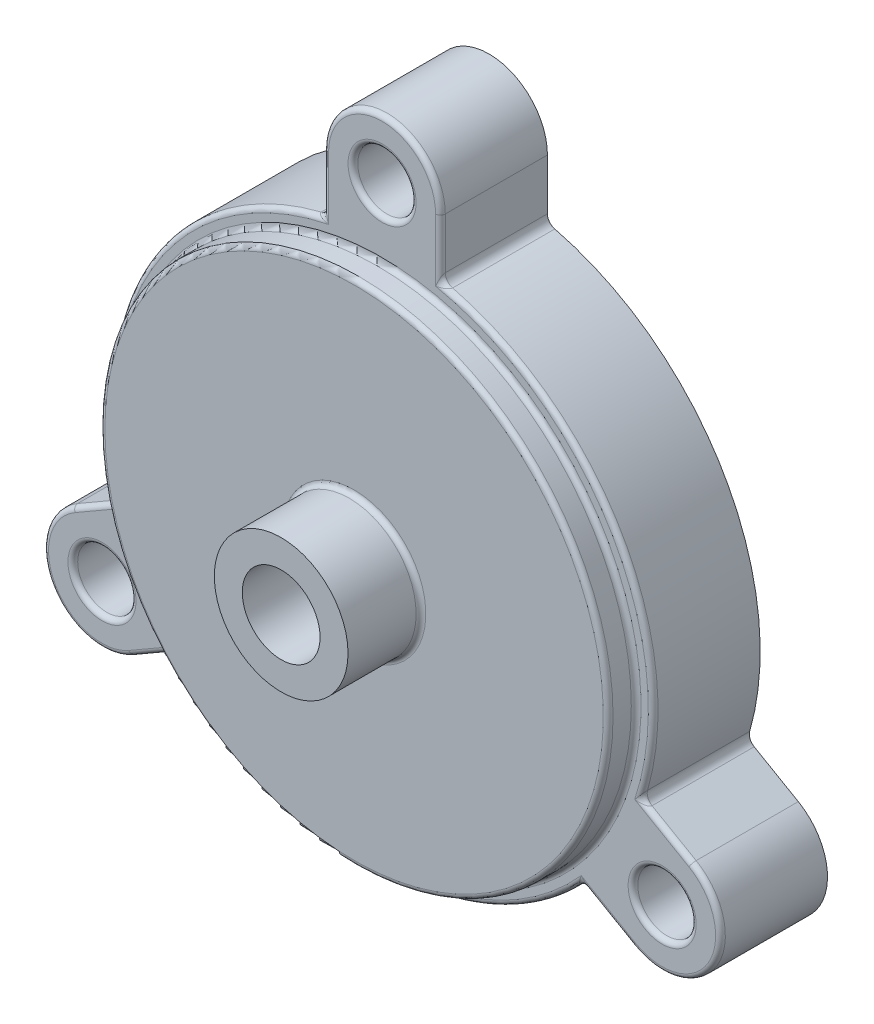
SolidWorks part; units mm, degrees
material "PE Low/Medium Density"
ref_plane "Front Plane" through (0, 0, 0) normal (0, 0, 1) x (1, 0, 0)
ref_plane "Top Plane" through (0, 0, 0) normal (0, 1, 0) x (1, 0, 0)
ref_plane "Right Plane" through (0, 0, 0) normal (1, 0, 0) x (0, 0, -1)
sketch "Sketch1" plane through (0, 0, 0) normal (1, 0, 0) x (0, 0, -1)
  line L0 (1.4605, 14.1605) -> (1.4605, 13.2715)
  line L1 (0, 0) -> (7.62, 0) construction
  line L2 (0, 12.2555) -> (0, 13.2715)
  line L3 (1.4605, 14.1605) -> (7.0485, 14.1605)
  line L4 (7.62, 12.2555) -> (7.62, 12.9159)
  line L5 (1.4605, 13.2715) -> (0, 13.2715)
  line L6 (7.0485, 14.1605) -> (7.0485, 12.9159)
  line L7 (7.0485, 12.9159) -> (7.62, 12.9159)
  line L8 (0, 12.2555) -> (0, 0)
  line L9 (0, 0) -> (1.4605, 0)
  line L10 (7.62, 12.2555) -> (1.4605, 12.2555)
  line L11 (1.4605, 12.2555) -> (1.4605, 0)
  dimension "D1" = 5.588
  dimension "D2" = 7.62
  dimension "D3" = 0.5715
  dimension "D4" = 14.1605
  dimension "D5" = 1.016
  dimension "D6" = 1.905
  dimension "D7" = 0.6604
revolve "Base revolve" add sketch "Sketch1" angle 360 about L1
sketch "Sketch3" plane through (0, 0, -7.0485) normal (0, 0, -1) x (-1, 0, 0)
  line L0 (-3.048, 16.891) -> (-3.048, 13.8286)
  line L1 (3.048, 16.891) -> (3.048, 13.8286)
  line L2 (0, 0) -> (0, 22.6145) construction
  arc A0 (3.048, 16.891) -> (-3.048, 16.891) centre (0, 16.891) ccw
  circle A1 centre (0, 0) radius 14.1605 construction
  circle A2 centre (0, 16.891) radius 1.524
  arc A3 (-3.048, 13.8286) -> (3.048, 13.8286) centre (0, 0) cw
  point P12 (0, 19.939)
  dimension "D1" = 3.048
  dimension "D2" = 3.048
  dimension "D3" = 16.891
extrude "Flange" add sketch "Sketch3" against normal up to surface (5.588 mm away) up to face at (13.2715, 0, -1.4605)
pattern_circular "Circular pattern for flanges" count 3 over 360 about axis through (0, 0, -1.4605) along (0, 0, 1) of "Flange"
sketch "Sketch4" plane through (0, 0, -7.62) normal (0, 0, -1) x (-1, 0, 0)
  line L0 (-1.524, 14.2514) -> (-1.524, 12.1604)
  line L1 (1.524, 14.2514) -> (1.524, 12.1604)
  line L2 (-1.524, 16.891) -> (-1.524, 14.2514) construction
  line L3 (1.524, 16.891) -> (1.524, 14.2514) construction
  arc A0 (-1.524, 14.2514) -> (1.524, 14.2514) centre (0, 16.891) ccw
  circle A1 centre (0, 16.891) radius 1.524 construction
  circle A2 centre (0, 0) radius 12.2555 construction
  circle A3 centre (0, 0) radius 12.2555 construction
  arc A4 (-1.524, 12.1604) -> (1.524, 12.1604) centre (0, 0) cw
extrude "Flange cut" cut sketch "Sketch4" against normal blind 5.842
pattern_circular "Circular pattern for flange cut" count 3 over 360 about axis through (0, 0, -7.0485) along (0, 0, 1) of "Flange cut"
sketch "Sketch5" plane through (0, 0, 0) normal (0, 0, 1) x (1, 0, 0)
  circle A0 centre (0, 0) radius 3.4925
  dimension "D1" = 6.985
extrude "Hub" add sketch "Sketch5" along normal blind 3.81 and the other way blind 2.921
sketch "Sketch6" plane through (0, 0, 3.81) normal (0, 0, 1) x (1, 0, 0)
  circle A0 centre (0, 0) radius 2.032
  dimension "D1" = 4.064
extrude "Bore" cut sketch "Sketch6" against normal through all
fillet "Touch-up fillets" radius 0.254 18 edges at (13.2715, 0, 0) (-3.4925, 0, 0) (13.104, -8.4455, -1.4605) (-16.152, -8.4455, -1.4605) (-1.524, 16.891, -1.4605) (-3.048, 15.3598, -1.4605) (0, 19.939, -1.4605) (3.048, 15.3598, -1.4605) (12.2634, 7.0803, -1.4605) (14.826, -5.0402, -1.4605) (17.2677, -9.9695, -1.4605) (11.778, -10.3195, -1.4605) (0, -14.1605, -1.4605) (-11.778, -10.3195, -1.4605) (-17.2677, -9.9695, -1.4605) (-14.826, -5.0402, -1.4605) (-12.2634, 7.0802, -1.4605) (13.2715, 0, -1.4605)
fillet "Flange fillet" radius 0.508 12 edges at (-3.0105, 13.7984, -1.5817) (-13.455, -4.292, -1.5817) (-10.4445, -9.5064, -1.5817) (10.4445, -9.5064, -1.5817) (13.455, -4.292, -1.5817) (3.0105, 13.7984, -1.5817) (-3.048, 13.8286, -4.3815) (-13.4999, -4.2746, -4.3815) (-10.4519, -9.5539, -4.3815) (10.4519, -9.5539, -4.3815) (13.4999, -4.2746, -4.3815) (3.048, 13.8286, -4.3815)
